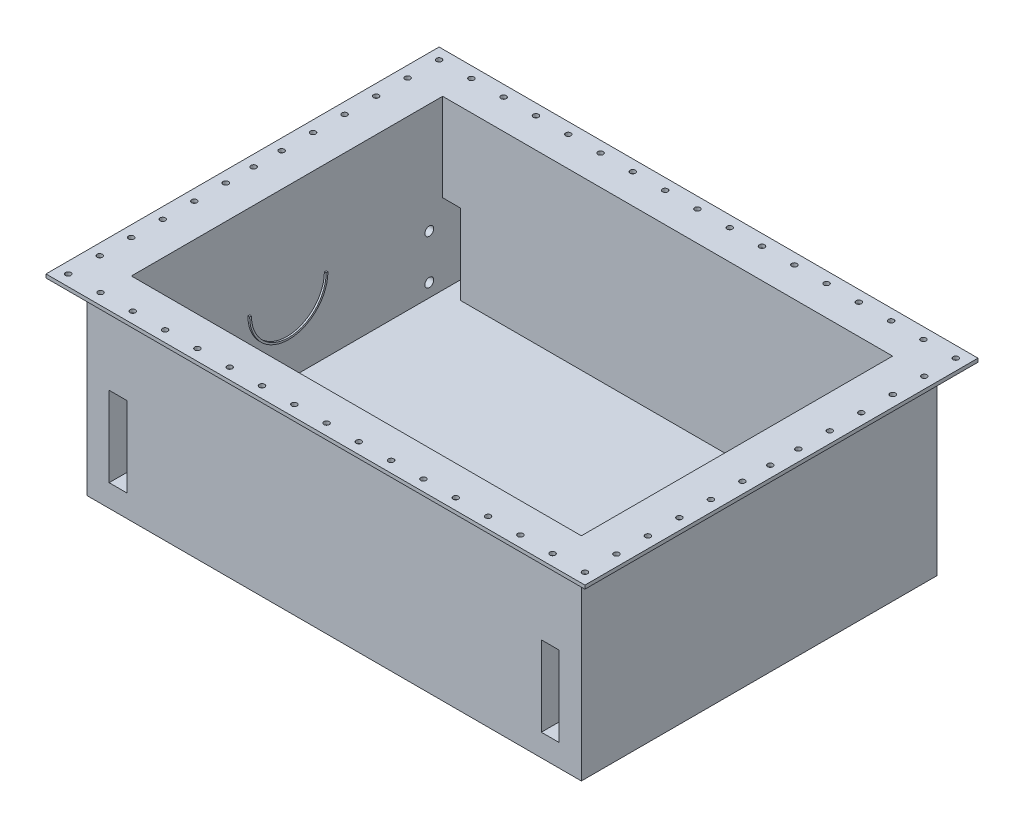
SolidWorks part; units mm, degrees
ref_plane "Front Plane" through (0, 0, 0) normal (0, 0, 1) x (1, 0, 0)
ref_plane "Top Plane" through (0, 0, 0) normal (0, 1, 0) x (1, 0, 0)
ref_plane "Right Plane" through (0, 0, 0) normal (1, 0, 0) x (0, 0, -1)
sketch "Sketch2" plane through (0, 0, 0) normal (0, 1, 0) x (1, 0, 0)
  line L0 (0, 437.5) -> (0, -437.5) construction
  line L1 (-632.5, 437.5) -> (632.5, 437.5)
  line L2 (-632.5, 437.5) -> (-632.5, -437.5)
  line L3 (-632.5, -437.5) -> (632.5, -437.5)
  line L4 (632.5, 437.5) -> (632.5, -437.5)
  line L5 (-632.5, 0) -> (632.5, 0) construction
  line L6 (-695, 48.7342) -> (-632.5, 48.7342) construction
  line L7 (-695, 500) -> (695, 500)
  line L8 (-695, 500) -> (-695, -500)
  line L9 (-695, -500) -> (695, -500)
  line L10 (695, 500) -> (695, -500)
  line L11 (632.5, 75.1796) -> (695, 75.1796) construction
  line L12 (-4.9015, 500) -> (-4.9015, 437.5) construction
  line L13 (-4.9015, -437.5) -> (-4.9015, -500) construction
  dimension "D1" = 62.5
  dimension "D2" = 1000
  dimension "D3" = 1390
extrude "Boss-Extrude1" add sketch "Sketch2" against normal blind 534.5
sketch "Sketch3" plane through (0, -534.5, 0) normal (0, -1, 0) x (1, 0, 0)
  line L0 (-695, 500) -> (-695, -500)
  line L3 (-695, 500) -> (695, 500)
  line L4 (695, -500) -> (695, 500)
  line L5 (-695, -500) -> (695, -500)
  line L6 (695, 500) -> (695, -500) construction
  line L7 (-695, 500) -> (695, 500) construction
  line L8 (-695, -500) -> (-695, 500) construction
  line L9 (695, -500) -> (-695, -500) construction
extrude "Boss-Extrude2" add sketch "Sketch3" against normal blind 62.5
sketch "Sketch4" plane through (695, 0, 0) normal (1, 0, 0) x (0, 0, -1)
  line L1 (0, 0) -> (0, -580.2055) construction
  line L2 (-105, -261) -> (-110, -261)
  line L3 (105, -261) -> (110, -261)
  arc A0 (-105, -261) -> (105, -261) centre (0, -261) ccw
  arc A1 (-110, -261) -> (110, -261) centre (0, -261) ccw
  dimension "D2" = 210
  dimension "D3" = 220
  dimension "D1" = 261
extrude "MMRTG Holder" add sketch "Sketch4" against normal blind 5 from offset 62.5 offset against normal yes
mirror "Mirror1" about plane through (0, 0, 0) normal (1, 0, 0) of "MMRTG Holder"
sketch "Sketch5" plane through (695, 0, 0) normal (1, 0, 0) x (0, 0, -1)
  line L0 (0, 70.8163) -> (0, -598.8061) construction
  line L1 (-500, -534.5) -> (500, -534.5) construction
  line L2 (-500, -534.5) -> (-500, 0) construction
  line L3 (-400, 39.1953) -> (-400, -618.3368) construction
  circle A0 centre (-400, -309.5) radius 12.5
  circle A1 centre (-400, -434.5) radius 12.5
  circle A2 centre (400, -434.5) radius 12.5
  circle A3 centre (400, -309.5) radius 12.5
  dimension "D4" = 25
  dimension "D1" = 125
  dimension "D2" = 100
  dimension "D3" = 100
extrude "Suspension Bolt Holes" cut sketch "Sketch5" against normal through all
sketch "Sketch6" plane through (0, 0, -500) normal (0, 0, -1) x (-1, 0, 0)
  line L0 (-695, -534.5) -> (-695, 0) construction
  line L1 (-632.5, -472) -> (-582.5, -472)
  line L2 (-632.5, -472) -> (-632.5, -247)
  line L3 (-632.5, -247) -> (-582.5, -247)
  line L4 (-582.5, -472) -> (-582.5, -247)
  line L5 (-695, -534.5) -> (695, -534.5) construction
  dimension "D1" = 62.5
  dimension "D2" = 62.5
  dimension "D3" = 50
  dimension "D4" = 225
extrude "Control Arm Cutout" cut sketch "Sketch6" against normal up to next
mirror "Mirror2" about plane through (0, 0, 0) normal (1, 0, 0) of "Control Arm Cutout"
mirror "Mirror3" about plane through (0, 0, 0) normal (0, 0, 1) of "Mirror2", "Control Arm Cutout"
sketch "Sketch7" plane through (0, 0, 0) normal (0, 1, 0) x (1, 0, 0)
  line L0 (695, 500) -> (-695, 500) construction
  line L1 (-757.5, 552.5) -> (757.5, 552.5)
  line L2 (-757.5, 552.5) -> (-757.5, -552.5)
  line L3 (-757.5, -552.5) -> (757.5, -552.5)
  line L4 (757.5, 552.5) -> (757.5, -552.5)
  line L5 (695, -500) -> (695, 500) construction
  line L7 (0, 552.5) -> (0, 500) construction
  line L8 (-632.5, 437.5) -> (632.5, 437.5)
  line L10 (0, -552.5) -> (0, -500) construction
  line L11 (-695, -500) -> (695, -500) construction
  line L12 (-632.5, 437.5) -> (-632.5, -437.5)
  line L13 (-632.5, -437.5) -> (632.5, -437.5)
  line L14 (632.5, 437.5) -> (632.5, -437.5)
  dimension "D1" = 52.5
  dimension "D2" = 62.5
  dimension "D3" = 52.5
extrude "AttachRoverFlange" add sketch "Sketch7" against normal blind 10
sketch "Sketch10" plane through (0, 0, 0) normal (0, 1, 0) x (1, 0, 0)
  line L0 (-726.25, 521.25) -> (-726.25, -475.2943) construction
  line L1 (-757.5, 552.5) -> (-757.5, -552.5) construction
  line L2 (757.5, 552.5) -> (-757.5, 552.5) construction
  line L3 (0, 0) -> (-1003.0581, 0) construction
  line L4 (-733.75, 0) -> (-718.75, 0)
  line L5 (0, 0) -> (0, 752.0536) construction
  line L6 (-726.25, 521.25) -> (0, 521.25) construction
  line L7 (0, 538.75) -> (0, 523.75)
  circle A0 centre (-726.25, 521.25) radius 7.5
  circle A1 centre (-726.25, 432.7083) radius 7.5
  circle A2 centre (-726.25, 344.1667) radius 7.5
  circle A3 centre (-726.25, 255.625) radius 7.5
  circle A4 centre (-635.4688, 521.25) radius 7.5
  circle A5 centre (-726.25, 167.0833) radius 7.5
  circle A6 centre (-726.25, 78.5417) radius 7.5
  circle A7 centre (-726.25, 0) radius 7.5
  circle A8 centre (-544.6875, 521.25) radius 7.5
  circle A9 centre (-453.9062, 521.25) radius 7.5
  circle A10 centre (-363.125, 521.25) radius 7.5
  circle A11 centre (-272.3438, 521.25) radius 7.5
  circle A12 centre (-181.5625, 521.25) radius 7.5
  circle A13 centre (0, 521.25) radius 7.5
  circle A14 centre (-90.7813, 521.25) radius 7.5
  circle A15 centre (90.7813, 521.25) radius 7.5
  circle A16 centre (181.5625, 521.25) radius 7.5
  circle A17 centre (272.3438, 521.25) radius 7.5
  circle A18 centre (363.125, 521.25) radius 7.5
  circle A19 centre (453.9062, 521.25) radius 7.5
  circle A20 centre (544.6875, 521.25) radius 7.5
  circle A21 centre (635.4688, 521.25) radius 7.5
  circle A22 centre (726.25, 521.25) radius 7.5
  circle A23 centre (726.25, 0) radius 7.5
  circle A24 centre (726.25, 78.5417) radius 7.5
  circle A25 centre (726.25, 167.0833) radius 7.5
  circle A26 centre (726.25, 255.625) radius 7.5
  circle A27 centre (726.25, 344.1667) radius 7.5
  circle A28 centre (726.25, 432.7083) radius 7.5
  circle A29 centre (726.25, -78.5417) radius 7.5
  circle A30 centre (726.25, -167.0833) radius 7.5
  circle A31 centre (726.25, -255.625) radius 7.5
  circle A32 centre (726.25, -344.1667) radius 7.5
  circle A33 centre (726.25, -432.7083) radius 7.5
  circle A34 centre (726.25, -521.25) radius 7.5
  circle A35 centre (635.4688, -521.25) radius 7.5
  circle A36 centre (544.6875, -521.25) radius 7.5
  circle A37 centre (453.9063, -521.25) radius 7.5
  circle A38 centre (363.125, -521.25) radius 7.5
  circle A39 centre (272.3438, -521.25) radius 7.5
  circle A40 centre (181.5625, -521.25) radius 7.5
  circle A41 centre (90.7813, -521.25) radius 7.5
  circle A42 centre (0, -521.25) radius 7.5
  circle A43 centre (-90.7812, -521.25) radius 7.5
  circle A44 centre (-181.5625, -521.25) radius 7.5
  circle A45 centre (-272.3437, -521.25) radius 7.5
  circle A46 centre (-363.125, -521.25) radius 7.5
  circle A47 centre (-453.9062, -521.25) radius 7.5
  circle A48 centre (-544.6875, -521.25) radius 7.5
  circle A49 centre (-635.4687, -521.25) radius 7.5
  circle A50 centre (-726.25, -521.25) radius 7.5
  circle A51 centre (-726.25, -344.1667) radius 7.5
  circle A52 centre (-726.25, -432.7083) radius 7.5
  circle A53 centre (-726.25, -255.625) radius 7.5
  circle A54 centre (-726.25, -167.0833) radius 7.5
  circle A55 centre (-726.25, -78.5417) radius 7.5
  dimension "D1" = 15
  dimension "D2" = 31.25
  dimension "D3" = 31.25
  dimension "D4" = 88.5417
  dimension "D5" = 88.5417
  dimension "D6" = 88.5417
  dimension "D7" = 88.5417
  dimension "D8" = 88.5417
  dimension "D9" = 90.7812
  dimension "D10" = 90.7812
  dimension "D11" = 90.7812
  dimension "D12" = 90.7812
  dimension "D13" = 90.7812
  dimension "D14" = 90.7812
  dimension "D15" = 90.7812
extrude "Attachment Holes" cut sketch "Sketch10" against normal up to next (10 mm away) contours L4 A7 | L4 A7 | A6 | A5 | A3 | A2 | A1 | A0 | A4 | A8 | A9 | A10 | A11 | A12 | A14 | L7 A13 | L7 A13 | A15 | A16 | A17 | A18 | A19 | A20 | A21 | A22 | A28 | A27 | A26 | A25 | A24 | A23 | A29 | A30 | A31 | A32 | A33 | A34 | A35 | A36 | A39 | A38 | A37 | A42 | A41 | A40 | A43 | A44 | A45 | A46 | A47 | A48 | A49 | A50 | A52 | A51 | A55 | A54 | A53 region at (-726.25, 0, -3.1831) region at (-726.25, 0, 3.1831) region at (-726.25, 0, -521.25) region at (-726.25, 0, -432.7083) region at (-726.25, 0, -344.1667) region at (-726.25, 0, -255.625) region at (-635.4688, 0, -521.25) region at (-726.25, 0, -167.0833) region at (-726.25, 0, -78.5417) region at (-544.6875, 0, -521.25) region at (-453.9062, 0, -521.25) region at (-363.125, 0, -521.25) region at (-272.3438, 0, -521.25) region at (-181.5625, 0, -521.25) region at (0, 0, -521.25) region at (-90.7813, 0, -521.25) region at (90.7813, 0, -521.25) region at (181.5625, 0, -521.25) region at (272.3438, 0, -521.25) region at (363.125, 0, -521.25) region at (453.9062, 0, -521.25) region at (544.6875, 0, -521.25) region at (635.4688, 0, -521.25) region at (726.25, 0, -521.25) region at (726.25, 0, 0) region at (726.25, 0, -78.5417) region at (726.25, 0, -167.0833) region at (726.25, 0, -255.625) region at (726.25, 0, -344.1667) region at (726.25, 0, -432.7083) region at (726.25, 0, 78.5417) region at (726.25, 0, 167.0833) region at (726.25, 0, 255.625) region at (726.25, 0, 344.1667) region at (726.25, 0, 432.7083) region at (726.25, 0, 521.25) region at (635.4688, 0, 521.25) region at (544.6875, 0, 521.25) region at (453.9063, 0, 521.25) region at (363.125, 0, 521.25) region at (272.3438, 0, 521.25) region at (181.5625, 0, 521.25) region at (90.7813, 0, 521.25) region at (0, 0, 521.25) region at (-90.7812, 0, 521.25) region at (-181.5625, 0, 521.25) region at (-272.3437, 0, 521.25) region at (-363.125, 0, 521.25) region at (-453.9062, 0, 521.25) region at (-544.6875, 0, 521.25) region at (-635.4687, 0, 521.25) region at (-726.25, 0, 521.25) region at (-726.25, 0, 344.1667) region at (-726.25, 0, 432.7083) region at (-726.25, 0, 255.625) region at (-726.25, 0, 167.0833) region at (-726.25, 0, 78.5417)
sketch "Sketch11" plane through (695, 0, 0) normal (1, 0, 0) x (0, 0, -1)
  circle A0 centre (-400, -309.5) radius 12.5
  circle A1 centre (-400, -434.5) radius 12.5
  circle A2 centre (400, -309.5) radius 12.5
  circle A3 centre (400, -434.5) radius 12.5
  circle A4 centre (400, -309.5) radius 12.5 construction
  circle A5 centre (400, -434.5) radius 12.5 construction
  circle A6 centre (-400, -309.5) radius 12.5 construction
  circle A7 centre (-400, -434.5) radius 12.5 construction
  point P10 (357.812, -310.0592)
extrude "Boss-Extrude3" add sketch "Sketch11" against normal blind 5
mirror "Mirror4" about plane through (0, 0, 0) normal (1, 0, 0) of "Boss-Extrude3"
equation "\"D3@Sketch2\"=1140+(4*(62.5))"
equation "\"D1@Boss-Extrude1\"=422+62.5+50"
equation "\"D4@Sketch10\"=531.25/6"
equation "\"D5@Sketch10\"=531.25/6"
equation "\"D6@Sketch10\"=531.25/6"
equation "\"D7@Sketch10\"=531.25/6"
equation "\"D8@Sketch10\"=531.25/6"
equation "\"D9@Sketch10\"=726.25/8"
equation "\"D10@Sketch10\"=726.25/8"
equation "\"D11@Sketch10\"=726.25/8"
equation "\"D12@Sketch10\"=726.25/8"
equation "\"D13@Sketch10\"=726.25/8"
equation "\"D14@Sketch10\"=726.25/8"
equation "\"D15@Sketch10\"=726.25/8"
